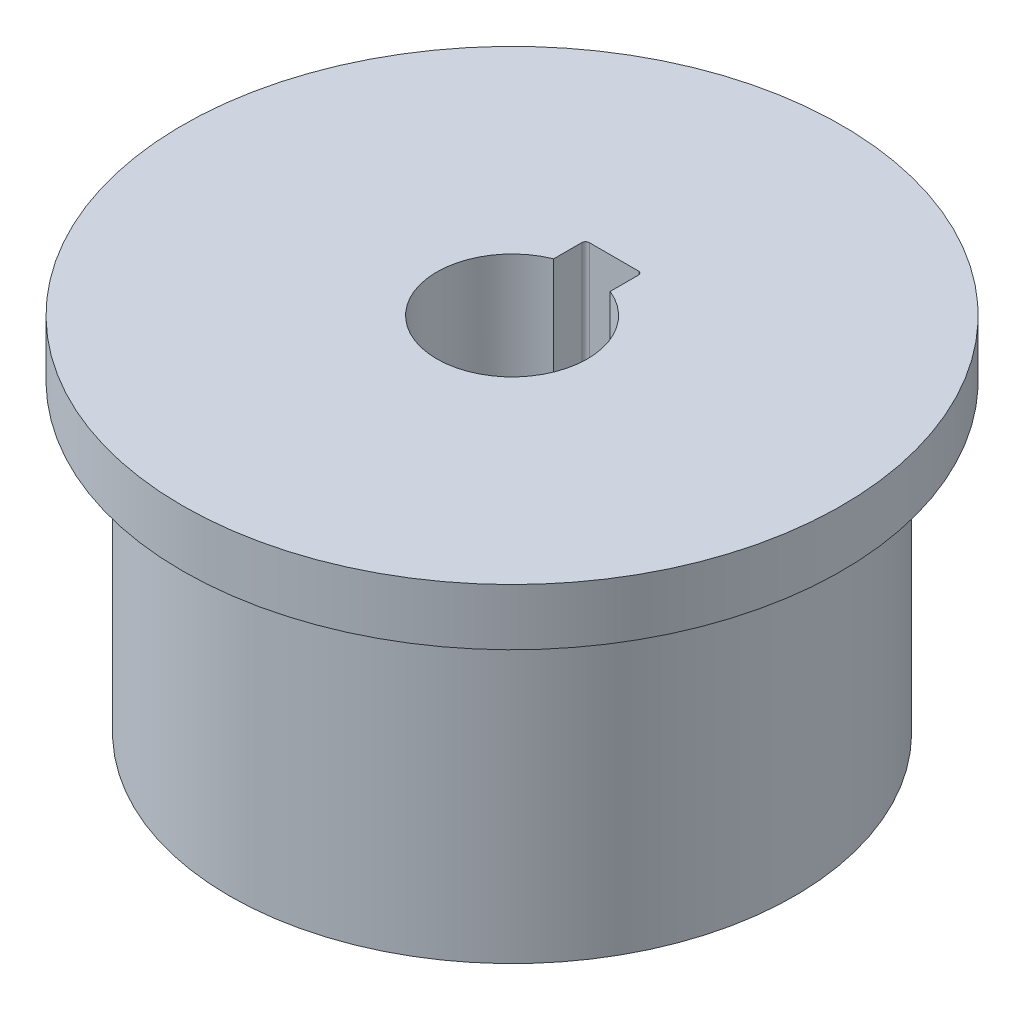
SolidWorks part; units mm, degrees
ref_plane "Plan de face" through (0, 0, 0) normal (0, 0, 1) x (1, 0, 0)
ref_plane "Plan de dessus" through (0, 0, 0) normal (0, 1, 0) x (1, 0, 0)
ref_plane "Plan de droite" through (0, 0, 0) normal (1, 0, 0) x (0, 0, -1)
sketch "Sketch1" plane through (0, 0, 0) normal (0, 0, 1) x (1, 0, 0)
  line L0 (0, 12.7093) -> (0, -8.2237) construction
  line L1 (4, 19.2) -> (17.5, 19.2)
  line L2 (17.5, 19.2) -> (17.5, 16.2)
  line L3 (17.5, 16.2) -> (15, 16.2)
  line L4 (15, 16.2) -> (15, 0)
  line L14 (4, -4) -> (4, 19.2)
  line L15 (4, -4) -> (5, -4)
  line L16 (8, -1) -> (8, 16.2)
  line L17 (15, 0) -> (12, 0)
  line L18 (12, 0) -> (12, 16.2)
  line L19 (12, 16.2) -> (8, 16.2)
  line L20 (5, -4) -> (8, -1)
  dimension "D1" = 16.2
  dimension "D2" = 3
  dimension "D3" = 17.5
  dimension "D4" = 15
  dimension "D5" = 4
  dimension "D6" = 3
  dimension "D7" = 1
  dimension "D8" = 45
  dimension "D9" = 8
  dimension "D10" = 4
revolve "Revolve1" add sketch "Sketch1" angle 360 about L0
sketch "Esquisse1" plane through (0, 19.2, 0) normal (0, 1, 0) x (1, 0, 0)
  line L0 (-1.5, 3.7081) -> (-1.5, 5.4)
  line L1 (-1.5, 5.4) -> (1.5, 5.4)
  line L2 (1.5, 5.4) -> (1.5, 3.7081)
  circle A1 centre (0, 0) radius 4 construction
  arc A2 (-1.5, 3.7081) -> (1.5, 3.7081) centre (0, 0) cw
  point P4 (0, 5.4)
  circle M2 centre (0, 0) radius 4
  dimension "D1" = 1.4
  dimension "D2" = 3
extrude "Enlèv. mat.-Extru.1" cut sketch "Esquisse1" against normal blind 15 contours L2 L1 L0 M2 region at (0, 19.2, -4.6496)
fillet "Congé1" radius 0.2 2 edges at (1.5, 11.7, -5.4) (-1.5, 11.7, -5.4)
